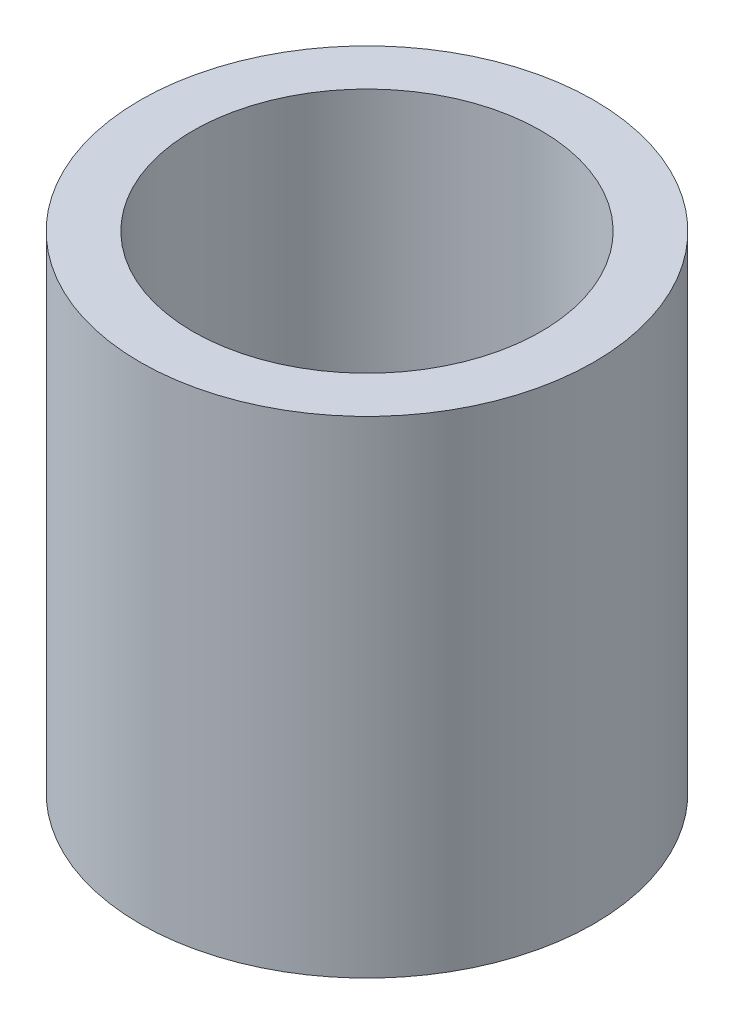
SolidWorks part; units mm, degrees
ref_plane "Front Plane" through (0, 0, 0) normal (0, 0, 1) x (1, 0, 0)
ref_plane "Top Plane" through (0, 0, 0) normal (0, 1, 0) x (1, 0, 0)
ref_plane "Right Plane" through (0, 0, 0) normal (1, 0, 0) x (0, 0, -1)
sketch "Sketch1" plane through (0, 0, 0) normal (0, 1, 0) x (1, 0, 0)
  circle A0 centre (0, 0) radius 12.5
  dimension "SLEEVE_OD" = 25
extrude "Boss-Extrude1" add sketch "Sketch1" along normal blind 26.7993
sketch "Sketch2" plane through (0, 0, 0) normal (0, 1, 0) x (1, 0, 0)
  circle A0 centre (0, 0) radius 9.5888
  dimension "BORE_D" = 19.1776
extrude "Cut-Extrude1" cut sketch "Sketch2" along normal through all
chamfer "Chamfer1" distance 2.4947 angle 52.533 rebuild error yes
